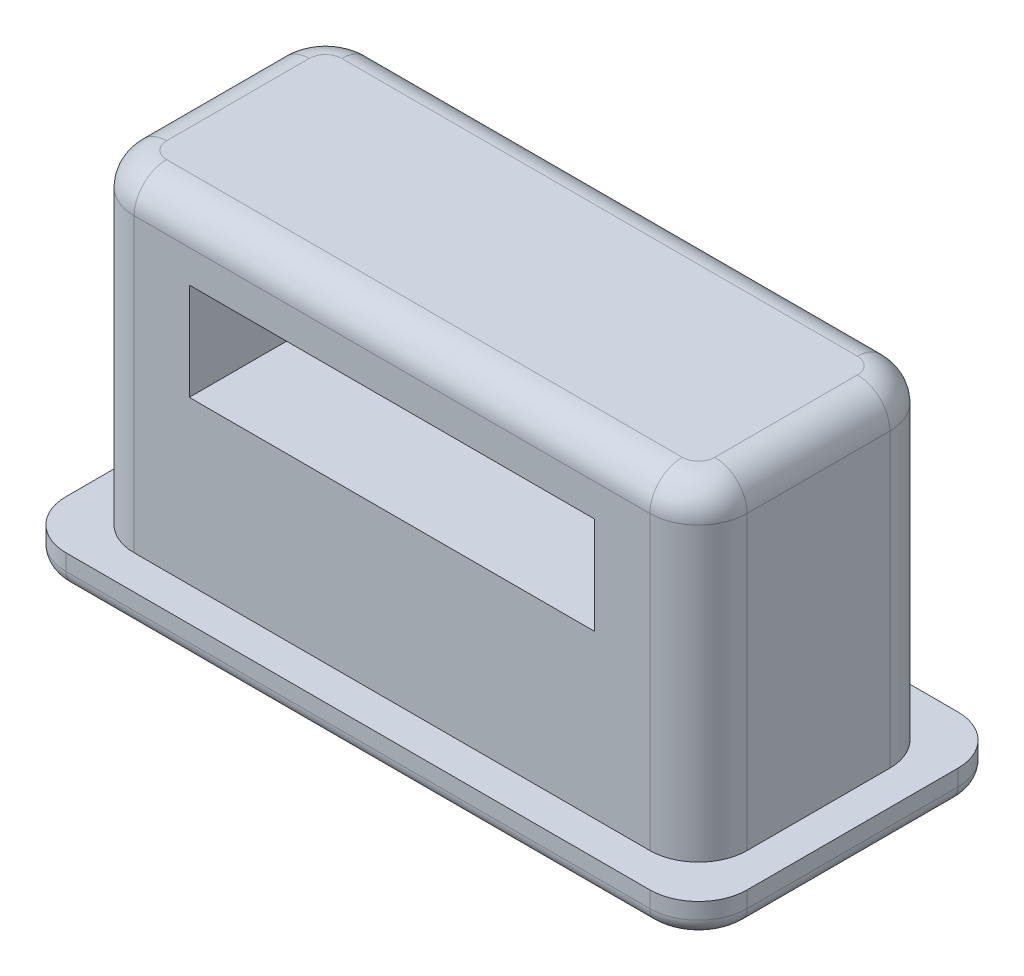
SolidWorks part; units mm, degrees
ref_plane "Front Plane" through (0, 0, 0) normal (0, 0, 1) x (1, 0, 0)
ref_plane "Top Plane" through (0, 0, 0) normal (0, 1, 0) x (1, 0, 0)
ref_plane "Right Plane" through (0, 0, 0) normal (1, 0, 0) x (0, 0, -1)
sketch "Sketch1" plane through (0, 0, 0) normal (0, 1, 0) x (1, 0, 0)
  line L1 (-56.7477, 15.4606) -> (-14.7477, 15.4606)
  line L2 (-56.7477, 15.4606) -> (-56.7477, -3.5394)
  line L3 (-56.7477, -3.5394) -> (-14.7477, -3.5394)
  line L4 (-14.7477, 15.4606) -> (-14.7477, -3.5394)
  dimension "D1" = 42
  dimension "D2" = 19
extrude "Boss-Extrude1" add sketch "Sketch1" along normal blind 2
fillet "Fillet1" radius 3 4 edges at (-56.7477, 1, -15.4606) (-56.7477, 1, 3.5394) (-14.7477, 1, -15.4606) (-14.7477, 1, 3.5394)
fillet "Fillet2" radius 1 8 edges at (-55.869, 0, 2.6607) (-56.7477, 0, -5.9606) (-55.869, 0, -14.5819) (-35.7477, 0, -15.4606) (-15.6264, 0, -14.5819) (-14.7477, 0, -5.9606) (-15.6264, 0, 2.6607) (-35.7477, 0, 3.5394)
sketch "Sketch2" plane through (0, 2, 0) normal (0, 1, 0) x (1, 0, 0)
  line L0 (-17.7477, 15.4606) -> (-53.7477, 15.4606) construction
  line L1 (-54.6477, 13.3606) -> (-16.8477, 13.3606)
  line L2 (-54.6477, 13.3606) -> (-54.6477, -1.4394)
  line L3 (-54.6477, -1.4394) -> (-16.8477, -1.4394)
  line L4 (-16.8477, 13.3606) -> (-16.8477, -1.4394)
  line L5 (-56.7477, 12.4606) -> (-56.7477, -0.5394) construction
  dimension "D1" = 37.8
  dimension "D2" = 14.8
  dimension "D3" = 2.1
  dimension "D4" = 2.1
extrude "Boss-Extrude2" add sketch "Sketch2" along normal blind 10
sketch "Sketch3" plane through (0, 12, 0) normal (0, 1, 0) x (1, 0, 0)
  line L0 (-48.2477, 13.3606) -> (-48.2477, -1.4394) construction
  line L1 (-16.8477, 13.3606) -> (-54.6477, 13.3606) construction
  line L2 (-54.6477, -1.4394) -> (-16.8477, -1.4394) construction
  line L3 (-54.6477, 13.3606) -> (-54.6477, -1.4394) construction
  line L4 (-23.2477, 13.3606) -> (-23.2477, -1.4394) construction
  line L5 (-16.8477, -1.4394) -> (-16.8477, 13.3606) construction
  line L9 (-23.2477, 13.3606) -> (-16.8477, 13.3606)
  line L10 (-23.2477, 13.3606) -> (-23.2477, -1.4394)
  line L11 (-23.2477, -1.4394) -> (-16.8477, -1.4394)
  line L12 (-16.8477, 13.3606) -> (-16.8477, -1.4394)
  line L13 (-54.6477, 13.3606) -> (-48.2477, 13.3606)
  line L14 (-54.6477, 13.3606) -> (-54.6477, -1.4394)
  line L15 (-54.6477, -1.4394) -> (-48.2477, -1.4394)
  line L16 (-48.2477, 13.3606) -> (-48.2477, -1.4394)
  dimension "D1" = 6.4
  dimension "D2" = 6.4
extrude "Boss-Extrude3" add sketch "Sketch3" along normal blind 10
sketch "Sketch5" plane through (-48.2477, 0, 0) normal (1, 0, 0) x (0, 0, -1)
  line L1 (-1.4394, 22) -> (13.3606, 22)
  line L2 (-1.4394, 22) -> (-1.4394, 18)
  line L3 (-1.4394, 18) -> (13.3606, 18)
  line L4 (13.3606, 22) -> (13.3606, 18)
  dimension "D1" = 14.8
  dimension "D2" = 4
extrude "Boss-Extrude4" add sketch "Sketch5" along normal up to surface (25 mm away) up to face at (-23.2477, 17, -5.9606)
fillet "Fillet4" radius 3 4 edges at (-16.8477, 12, -13.3606) (-16.8477, 12, 1.4394) (-54.6477, 12, -13.3606) (-54.6477, 12, 1.4394)
fillet "Fillet5" radius 2 8 edges at (-17.7264, 22, -12.4819) (-16.8477, 22, -5.9606) (-17.7264, 22, 0.5607) (-35.7477, 22, 1.4394) (-53.769, 22, 0.5607) (-54.6477, 22, -5.9606) (-53.769, 22, -12.4819) (-35.7477, 22, -13.3606)
